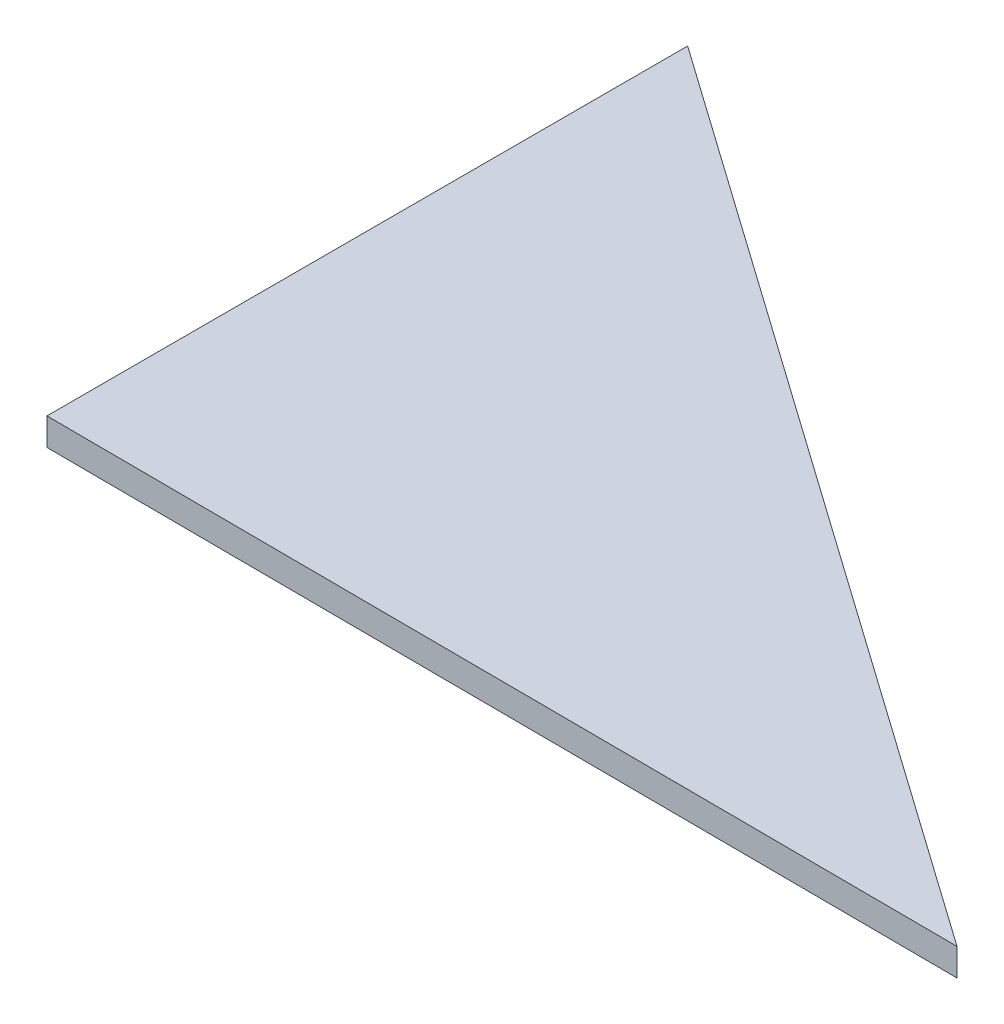
SolidWorks part; units mm, degrees
ref_plane "Front Plane" through (0, 0, 0) normal (0, 0, 1) x (1, 0, 0)
ref_plane "Top Plane" through (0, 0, 0) normal (0, 1, 0) x (1, 0, 0)
ref_plane "Right Plane" through (0, 0, 0) normal (1, 0, 0) x (0, 0, -1)
sketch "Sketch1" plane through (0, 0, 0) normal (0, 1, 0) x (1, 0, 0)
  line L1 (0, 0) -> (263.3435, 0)
  line L2 (0, 0) -> (0, 204.1914)
  line L3 (0, 204.1914) -> (263.3435, 204.1914)
  line L4 (263.3435, 0) -> (263.3435, 204.1914)
  line L5 (0, 0) -> (263.3435, 204.1914) construction
  line L6 (0, 204.1914) -> (263.3435, 0) construction
  point P4 (131.6717, 102.0957)
  dimension "D1" = 263.3435
  dimension "D2" = 204.1914
extrude "Boss-Extrude1" add sketch "Sketch1" along normal blind 4.6
sketch "Sketch2" plane through (0, 0, 0) normal (0, -1, 0) x (1, 0, 0)
  line L8 (0, -127.7494) -> (0, -20.0534)
  line L9 (0, -20.0534) -> (-4.5602, -20.0534)
  line L10 (-4.5602, -20.0534) -> (-4.5602, -127.7494)
  line L11 (-4.5602, -127.7494) -> (0, -127.7494)
  line L15 (0, -127.7494) -> (153.7152, -19.3145)
  line L16 (181.7546, 8.9697) -> (153.7152, -19.3145)
  line L17 (210.0043, -19.5267) -> (181.7546, 8.9697)
  line L18 (210.0043, -19.5267) -> (181.9649, -47.8109)
  line L19 (181.9649, -47.8109) -> (153.7152, -19.3145)
  line L21 (71.2201, -199.5914) -> (0, -127.7494)
  line L22 (0, -19.9863) -> (71.2201, 51.8558)
  line L25 (0, -20.0534) -> (153.7152, -19.3145)
  line M5 (0, 0) -> (0, -204.1914)
extrude "Cut-Extrude1" cut sketch "Sketch2" against normal through all flip side to cut contours L25 L15 M5 region at (51.2384, 0, -55.7057)
equation "\"MDF\"= 4.8mm"
equation "\"Foamcore\"= 4.6mm"
equation "\"GMaterial\"= \"MDF\""
equation "\"PCB\" = 1.6mm"
equation "\"BaseWidth\" = 10in"
equation "\"SkidLength\" = 1in"
equation "\"SkidClearance\" = 0.4in"
equation "\"MotorMountLength\" = 2in"
equation "\"MotorMountWidth\" = \"GMaterial\""
equation "\"MotorMountHeight\" = 2.25in"
equation "\"UnoStackWidth\" = 77.4mm"
equation "\"UnoStackLength\" = 79.8mm"
equation "\"UnoStackHeight\" = 34.2mm"
equation "\"TallHexRiserHeight\" = 22.2mm"
equation "\"PingPongBallSize\" = 40mm"
equation "\"BarrelLength\" = 9in"
equation "\"BarrelSize\" = \"PingPongBallSize\""
equation "\"PlatformLength\" = 4in"
equation "\"PlatformWidth\" = 6in"
equation "\"WheelDiameter\"=2.99213"
equation "\"ServoMountHeight\"=2.49223"
equation "\"ServoGearHeight\" = 0.95330261in"
equation "\"ServoMountLength\"= 1.53774"
equation "\"PivotHoleRadius\"= 0.616358"
equation "\"PlatformMountHeight\" = 3.19"
equation "\"TensionOffSet\"= .3mm"
equation "\"MotorMountWedge\"=0.333333"
equation "\"LaserCutterOffset\"= .3mm"
equation "\"BumperWidth\"=11"
equation "\"PitcherWheelCompression\" = 2.5mm"
equation "\"BarrelToHopperDistance\" = 0.5405in"
equation "\"PitchingWheelWidth\" = 26.2mm"
equation "\"PitchingWheelDiameter\" = 65.5mm"
equation "\"PitchingWheelMountOffset\" = 8.4mm"
equation "\"PitchingWheelInnerDiameter\" = 45.5mm"
equation "\"PitchingWheelBoltShoulder\" = 4.5mm"
equation "\"BrassCouplingLength\" = 18mm"
equation "\"PitchingMotorHeight\" = 57.0mm"
equation "\"PitchingMotorShaftTopHeight\" = \"PitchingMotorHeight\" - 44.1mm"
equation "\"PitchingMotorBodyHeight\" = 38mm"
equation "\"PitchingMotorTopShoulderHeight\" = 40.6mm - \"PitchingMotorBodyHeight\" "
equation "\"PitchingMotorBottomShoulderHeight\" = 40.2mm - \"PitchingMotorBodyHeight\""
equation "\"PitchingMotorBottomShaftHeight\" = \"PitchingMotorHeight\" - \"PitchingMotorShaftTopHeight\" - \"PitchingMotorTopShoulderHeight\" - \"PitchingMotorBodyHeight\" - \"PitchingMotorBottomShoulderHeight\""
equation "\"PitchingMotorShaftDiameter\" = 2.2mm"
equation "\"PitchingMotorBodyDiameter\" = 27.4mm"
equation "\"PitchingMotorTopShoulderDiameter\" = 9.8mm"
equation "\"PitchingMotorBottomShoulderDiameter\" = 9.8mm"
equation "\"BrassCouplingHexSize\" = 12mm"
equation "\"BrassCouplingBoreSize\" = 3.17mm"
equation "\"PitchingMotorMountingHoleDistance\" = 16mm"
equation "\"Acrylic\" = 4.4mm"
equation "\"PitchingMotorDistance\" = \"PitchingWheelDiameter\" + \"PingPongBallSize\" - \"PitcherWheelCompression\"*2"
equation "\"PitchingMotorPlatformOffset\"=1"
equation "\"ServoPlatformOffset\"=1.64173"
equation "\"BallBearingDiameter\" = 22mm"
equation "\"BallBearingWidth\" = 9mm"
equation "\"BallBearingHexShoulder\" = 9mm - 5.9mm"
equation "\"BallBearingHexSize\" = .36in"
equation "\"PlatformMountFootLength\"=0.857143"
equation "\"WheelWidth\"= 26mm"
equation "\"ServoMountReductionBackHeight\"=2.25"
equation "\"PlatformBottomWidthThird\" =  0.857143in"
equation "\"PlatformMountBackReductionHeight\"= 2.5in"
equation "\"PlatformMountBackReductionWidth\"= 3/7in"
equation "\"PlatformMountFrontReductionWidth\" =  1.46226in"
equation "\"PlatformMountFrontReductionHeight\" = 2.5in"
equation "\"HopperLongWallLength\" = 8.646in"
equation "\"HopperShortWallLength\" = 0.9571in"
equation "\"HopperHeight\" = 3.50in - \"Foamcore\""
equation "\"HoperLongSlantLength\" = 7.064in"
equation "\"HopperBottomTemplateWidth\" = 8.03903165in"
equation "\"HopperBottomTemplateLength\" = 10.367854in"
equation "\"D1@Sketch1\"=\"HopperBottomTemplateLength\""
equation "\"D2@Sketch1\"=\"HopperBottomTemplateWidth\""
equation "\"D1@Boss-Extrude1\"=\"Foamcore\""
